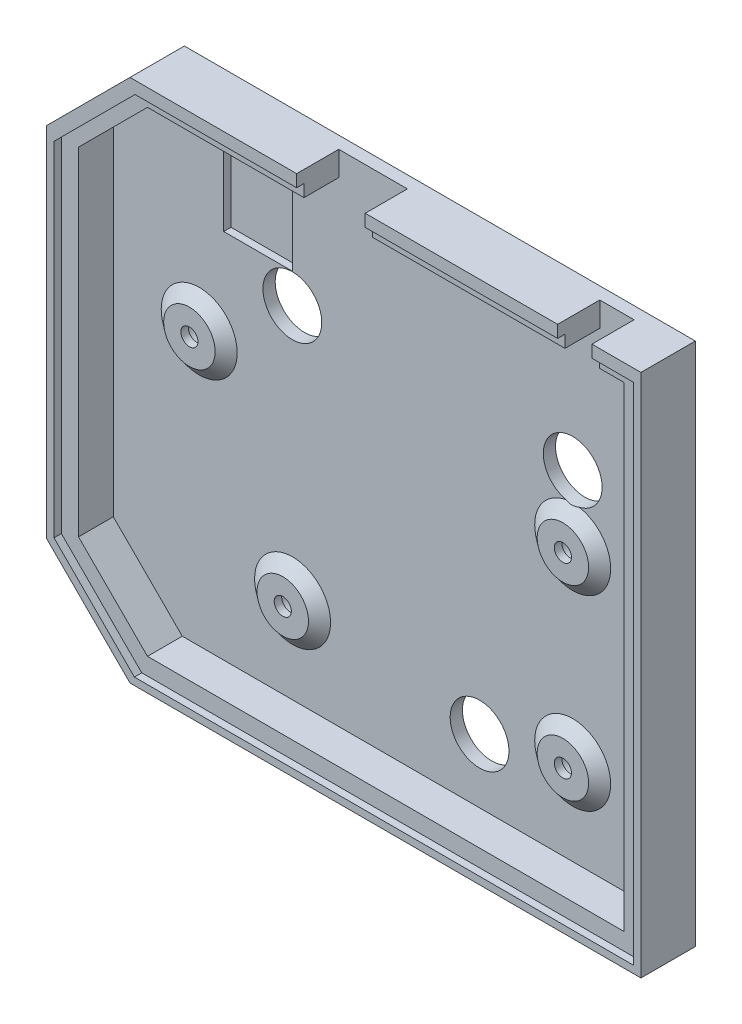
SolidWorks part; units mm, degrees
material "Delrin 2700 NC010, copolymère d'acétal à faible viscosité (SS)"
ref_plane "Plan de face" through (0, 0, 0) normal (0, 0, 1) x (1, 0, 0)
ref_plane "Plan de dessus" through (0, 0, 0) normal (0, 1, 0) x (1, 0, 0)
ref_plane "Plan de droite" through (0, 0, 0) normal (1, 0, 0) x (0, 0, -1)
sketch "Esquisse1" plane through (0, 0, 0) normal (0, 0, 1) x (1, 0, 0)
  line L0 (0, -85) -> (17, -102)
  line L4 (121.25, 5) -> (121.25, -102)
  line L5 (17, 5) -> (0, -12)
  line L7 (121.25, 5) -> (17, 5)
  line L8 (0, -12) -> (0, -85)
  line L9 (17, -102) -> (121.25, -102)
  dimension "D1" = 107
  dimension "D2" = 121.25
  dimension "D3" = 17
  dimension "D4" = 17
  dimension "D5" = 17
  dimension "D6" = 17
extrude "Boss.-Extru.1" add sketch "Esquisse1" along normal blind 2.5
sketch "Esquisse2" plane through (0, 0, 2.5) normal (0, 0, 1) x (1, 0, 0)
  line L0 (0, -12) -> (0, -85) construction
  line L1 (5, 0) -> (116.25, 0) construction
  line L2 (5, 0) -> (5, -97) construction
  line L3 (5, -97) -> (116.25, -97) construction
  line L4 (116.25, 0) -> (116.25, -97) construction
  line L5 (17, -102) -> (121.25, -102) construction
  line L6 (121.25, -102) -> (121.25, 5) construction
  line L7 (121.25, 5) -> (17, 5) construction
  line L9 (5, -82.9289) -> (19.0711, -97)
  line L10 (0, -85) -> (17, -102) construction
  line L11 (5, -14.0711) -> (19.0711, 0)
  line L12 (17, 5) -> (0, -12) construction
  line L14 (5, -14.0711) -> (5, -82.9289)
  line L15 (19.0711, -97) -> (116.25, -97)
  line L16 (121.25, 5) -> (121.25, -102) construction
  line L17 (121.25, -102) -> (17, -102)
  line L18 (17, -102) -> (0, -85)
  line L19 (0, -85) -> (0, -12)
  line L20 (0, -12) -> (17, 5)
  line L25 (51, 0) -> (51, 5)
  line L26 (65, 0) -> (65, 5)
  line L27 (19.0711, 0) -> (51, 0)
  line L28 (51, 5) -> (17, 5)
  line L38 (116.25, 0) -> (116.25, -97)
  line L39 (121.25, -102) -> (121.25, 5)
  line L40 (121.25, 5) -> (111.25, 5)
  line L41 (111.25, 5) -> (111.25, 0)
  line L42 (111.25, 0) -> (116.25, 0)
  line L43 (65, 0) -> (104.25, 0)
  line L44 (104.25, 0) -> (104.25, 5)
  line L45 (104.25, 5) -> (65, 5)
  point P33 (51, 0)
  point P34 (65, 0)
  dimension "D1" = 5
  dimension "D2" = 5
  dimension "D3" = 5
  dimension "D4" = 5
  dimension "D5" = 5
  dimension "D6" = 5
  dimension "D7" = 7
  dimension "D8" = 46
  dimension "D9" = 14
  dimension "D10" = 10
extrude "Boss.-Extru.2" add sketch "Esquisse2" along normal blind 8.6
sketch "Esquisse5" plane through (0, 0, 2.5) normal (0, 0, 1) x (1, 0, 0)
  line L0 (116.25, -97) -> (19.0711, -97) construction
  line L2 (116.25, 0) -> (116.25, -97) construction
  point P0 (22.525, -41.37)
  point P1 (98.725, -41.37)
  point P2 (98.725, -79.47)
  point P3 (41.575, -79.47)
  dimension "D1" = 38.1
  dimension "D2" = 17.53
  dimension "D3" = 17.525
  dimension "D4" = 76.2
  dimension "D5" = 57.15
ref_axis "Axe5" through (22.525, -41.37, 2.5) along (0, 0, 1)
ref_axis "Axe6" through (98.725, -41.37, 2.5) along (0, 0, 1)
ref_axis "Axe7" through (41.575, -79.47, 2.5) along (0, 0, 1)
ref_axis "Axe8" through (98.725, -79.47, 2.5) along (0, 0, 1)
sketch3d "Esquisse3D5"
  line L0 (22.525, -41.37, 2.5) -> (98.725, -41.37, 2.5) construction
  line L1 (41.575, -79.47, 2.5) -> (98.725, -79.47, 2.5) construction
ref_plane "Plan4" through (98.725, -41.37, 2.5) normal (1, 0, 0) x (0, 0, -1)
sketch "Esquisse8" plane through (98.725, -41.37, 2.5) normal (1, 0, 0) x (0, 0, -1)
  line L0 (0, 1.75) -> (0, 7.75)
  line L1 (0, 7.75) -> (-2, 5.25)
  line L2 (-2, 5.25) -> (-2, 1.75)
  line L3 (-2, 1.75) -> (0, 1.75)
  line L5 (0, 0) -> (-50.5083, 0) construction
  point P0 (0, 1.75)
  dimension "D1" = 6
  dimension "D2" = 3.5
  dimension "D3" = 2
  dimension "D4" = 1.75
revolve "Révolution3" add sketch "Esquisse8" angle 360 about axis through (98.725, -41.37, 2.5) along (0, 0, 1)
ref_plane "Plan5" through (41.575, -79.47, 2.5) normal (1, 0, 0) x (0, 0, -1)
sketch "Esquisse9" plane through (41.575, -79.47, 2.5) normal (1, 0, 0) x (0, 0, -1)
  line L0 (0, 1.75) -> (0, 7.75)
  line L1 (0, 7.75) -> (-2, 5.25)
  line L2 (-2, 5.25) -> (-2, 1.75)
  line L3 (-2, 1.75) -> (0, 1.75)
  point P0 (0, 1.75)
  dimension "D1" = 2
  dimension "D2" = 6
  dimension "D3" = 3.5
  dimension "D4" = 1.75
revolve "Révolution4" add sketch "Esquisse9" angle 360 about axis through (41.575, -79.47, 2.5) along (0, 0, 1)
ref_plane "Plan6" through (98.725, -79.47, 2.5) normal (1, 0, 0) x (0, 0, -1)
sketch "Esquisse10" plane through (98.725, -79.47, 2.5) normal (1, 0, 0) x (0, 0, -1)
  line L0 (0, 1.75) -> (0, 7.75)
  line L1 (0, 7.75) -> (-2, 5.25)
  line L2 (-2, 5.25) -> (-2, 1.75)
  line L3 (-2, 1.75) -> (0, 1.75)
  point P0 (0, 1.75)
  dimension "D1" = 6
  dimension "D2" = 2
  dimension "D3" = 3.5
  dimension "D4" = 1.75
revolve "Révolution5" add sketch "Esquisse10" angle 360 about axis through (98.725, -79.47, 2.5) along (0, 0, 1)
hole_wizard "Dégagement M32" positions "Esquisse15" profile "Esquisse16" hole size "M3" standard "Ansi Metric" end condition up to next
sketch "Esquisse15" plane through (0, 0, 2.5) normal (0, 0, 1) x (1, 0, 0)
  point P0 (22.525, -41.37)
  point P3 (41.575, -79.47)
  point P6 (98.725, -41.37)
  point P9 (98.725, -79.47)
sketch "Esquisse16" plane through (22.525, -41.37, 2.5) normal (1, 0, 0) x (0, -1, 0)
  line L0 (0, 0) -> (0, 2.5)
  line L1 (0, 2.5) -> (1.8, 2.5)
  line L2 (1.8, 2.5) -> (1.8, 0)
  line L5 (1.8, 0) -> (0, 0)
  line L11 (0, -6.35) -> (0, 107.95) construction
  dimension "Diamètre du perçage jusqu'au prochain" = 3.6
  dimension "Profondeur du perçage jusqu'au prochain" = 2.5
ref_plane "Plan7" through (22.525, -41.37, 2.5) normal (1, 0, 0) x (0, 0, -1)
sketch "Esquisse17" plane through (22.525, -41.37, 2.5) normal (1, 0, 0) x (0, 0, -1)
  line L1 (0, 1.75) -> (0, 7.75)
  line L2 (0, 7.75) -> (-2, 5.25)
  line L3 (-2, 5.25) -> (-2, 1.75)
  line L4 (-2, 1.75) -> (0, 1.75)
  line L5 (0, 0) -> (-49.8077, 0) construction
  dimension "D1" = 1.75
  dimension "D2" = 6
  dimension "D3" = 3.5
  dimension "D4" = 2
revolve "Révolution6" add sketch "Esquisse17" angle 360 about axis through (22.525, -41.37, 2.5) along (0, 0, 1)
ref_point "Point1"
ref_point "Point2"
ref_point "Point3"
ref_point "Point4"
sketch "Esquisse18" plane through (0, 0, 0) normal (0, 0, -1) x (-1, 0, 0)
  circle A0 centre (-22.525, -41.37) radius 2.7
  circle A1 centre (-98.725, -41.37) radius 2.7
  circle A2 centre (-41.575, -79.47) radius 2.7
  circle A3 centre (-98.725, -79.47) radius 2.7
  dimension "D1" = 5.4
  dimension "D2" = 5.4
  dimension "D4" = 5.4
  dimension "D3" = 5.4
extrude "Enlèv. mat.-Extru.2" cut sketch "Esquisse18" against normal blind 3
sketch "Esquisse20" plane through (0, 0, 11.1) normal (0, 0, 1) x (1, 0, 0)
  line L1 (119.75, 2.5) -> (18.0355, 2.5)
  line L2 (-695.6105, 613.0147) -> (34659.7285, -34742.3244) construction
  line L3 (0, -85) -> (17, -102) construction
  line L5 (121.25, -102) -> (121.25, 5) construction
  line L12 (104.25, 5) -> (65, 5) construction
  line L13 (1.5, 2.5) -> (119.75, 2.5) construction
  line L14 (1.5, 2.5) -> (1.5, -100.5) construction
  line L15 (1.5, -100.5) -> (119.75, -100.5) construction
  line L16 (119.75, 2.5) -> (119.75, -100.5) construction
  line L18 (17, -102) -> (121.25, -102) construction
  line L19 (0, -12) -> (0, -85) construction
  line L25 (119.75, -100.5) -> (119.75, 2.5)
  line L26 (39.1913, 23.6558) -> (-16.7593, -32.2949) construction
  line L27 (17, 5) -> (0, -12) construction
  line L28 (18.0355, 2.5) -> (1.5, -14.0355)
  line L30 (1.5, -14.0355) -> (1.5, -84.0958)
  line L31 (1.5, -84.0958) -> (17.9042, -100.5)
  line L32 (17.9042, -100.5) -> (119.75, -100.5)
  point P13 (0, 0)
  dimension "D1" = 2.5
  dimension "D2" = 1.5
  dimension "D3" = 1.5
  dimension "D4" = 1.5
  dimension "D5" = 2.5
  dimension "D6" = 1.7
extrude "Enlèv. mat.-Extru.3" cut sketch "Esquisse20" against normal blind 1.5
sketch "Esquisse21" plane through (0, 0, 2.5) normal (0, 0, 1) x (1, 0, 0)
  circle A0 centre (98.725, -27.87) radius 6
  circle A1 centre (41.525, -27.37) radius 6
  circle A2 centre (79.725, -83.97) radius 6
  dimension "D1" = 13.5
  dimension "D2" = 14
  dimension "D4" = 19
  dimension "D3" = 19
  dimension "D5" = 4.5
extrude "Enlèv. mat.-Extru.4" cut sketch "Esquisse21" against normal blind 10 and the other way through all
chamfer "Chanfrein2" distance 1 angle 30 4 edges at (96.025, -79.47, 3) (38.875, -79.47, 3) (19.825, -41.37, 3) (96.025, -41.37, 3) first distance on face at (96.975, -79.47, 3) first distance on face at (39.825, -79.47, 3) first distance on face at (20.775, -41.37, 3) first distance on face at (96.975, -41.37, 3)
sketch "Esquisse22" plane through (0, 0, 2.5) normal (0, 0, 1) x (1, 0, 0)
  line L1 (27.525, -1.27) -> (41.525, -1.27)
  line L2 (27.525, -1.27) -> (27.525, -21.27)
  line L3 (27.525, -21.27) -> (41.525, -21.27)
  line L4 (41.525, -1.27) -> (41.525, -21.27)
  circle A0 centre (22.525, -41.37) radius 1.75 construction
  point P5 (22.525, -41.37)
  dimension "D1" = 20.1
  dimension "D2" = 5
  dimension "D3" = 14
  dimension "D4" = 20
extrude "Enlèv. mat.-Extru.13" cut sketch "Esquisse22" against normal blind 1.5 contours L2 L3 L4 L1
equation "\"r_ext\"= 5.4"
equation "\"D1@Esquisse18\"=\"r_ext\""
equation "\"D2@Esquisse18\"=\"r_ext\""
equation "\"D4@Esquisse18\"=\"r_ext\""
equation "\"D3@Esquisse18\"=\"r_ext\""
